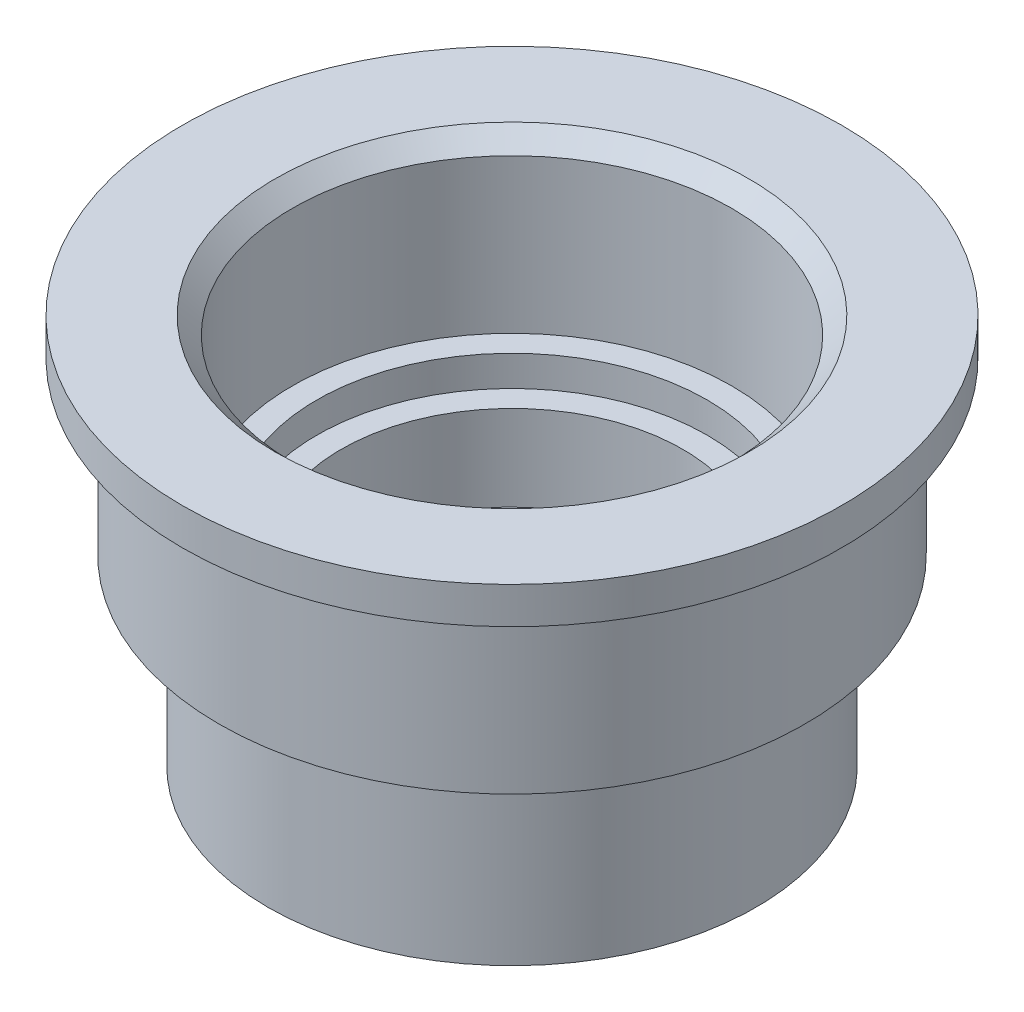
SolidWorks part; units mm, degrees
ref_plane "Plan de face" through (0, 0, 0) normal (0, 0, 1) x (1, 0, 0)
ref_plane "Plan de dessus" through (0, 0, 0) normal (0, 1, 0) x (1, 0, 0)
ref_plane "Plan de droite" through (0, 0, 0) normal (1, 0, 0) x (0, 0, -1)
sketch "Esquisse2" plane through (0, 0, 0) normal (0, 1, 0) x (1, 0, 0)
  circle A0 centre (0, 0) radius 10
  dimension "D1" = 20
extrude "Boss.-Extru.1" add sketch "Esquisse2" along normal blind 7.5 contours A0
sketch "Esquisse3" plane through (0, 7.5, 0) normal (0, 1, 0) x (1, 0, 0)
  circle A0 centre (0, 0) radius 12
  dimension "D1" = 24
extrude "Boss.-Extru.2" add sketch "Esquisse3" along normal blind 7 contours A0
sketch "Esquisse4" plane through (0, 14.5, 0) normal (0, 1, 0) x (1, 0, 0)
  circle A0 centre (0, 0) radius 13.5
  dimension "D1" = 27
extrude "Boss.-Extru.3" add sketch "Esquisse4" along normal blind 1.5 contours A0
sketch "Esquisse5" plane through (0, 0, 0) normal (0, -1, 0) x (1, 0, 0)
  circle A0 centre (0, 0) radius 8.8423
sketch "Esquisse7" plane through (0, 0, 0) normal (0, -1, 0) x (1, 0, 0)
  circle A0 centre (0, 0) radius 5.5
  dimension "D1" = 11
extrude "Enlèv. mat.-Extru.1" cut sketch "Esquisse7" against normal blind 21.5
sketch "Esquisse8" plane through (0, 16, 0) normal (0, 1, 0) x (1, 0, 0)
  circle A0 centre (0, 0) radius 9
  dimension "D1" = 18
extrude "Enlèv. mat.-Extru.2" cut sketch "Esquisse8" against normal blind 7 contours A0
chamfer "Chanfrein1" distance 0.7 angle 45 1 edges at (0, 16, 9)
sketch "Esquisse9" plane through (0, 9, 0) normal (0, 1, 0) x (1, 0, 0)
  circle A0 centre (0, 0) radius 8
  dimension "D1" = 16
extrude "Enlèv. mat.-Extru.3" cut sketch "Esquisse9" against normal blind 1.25
sketch "Esquisse10" plane through (0, 7.75, 0) normal (0, 1, 0) x (1, 0, 0)
  circle A0 centre (0, 0) radius 7
  dimension "D1" = 14
extrude "Enlèv. mat.-Extru.4" cut sketch "Esquisse10" against normal blind 3.5
